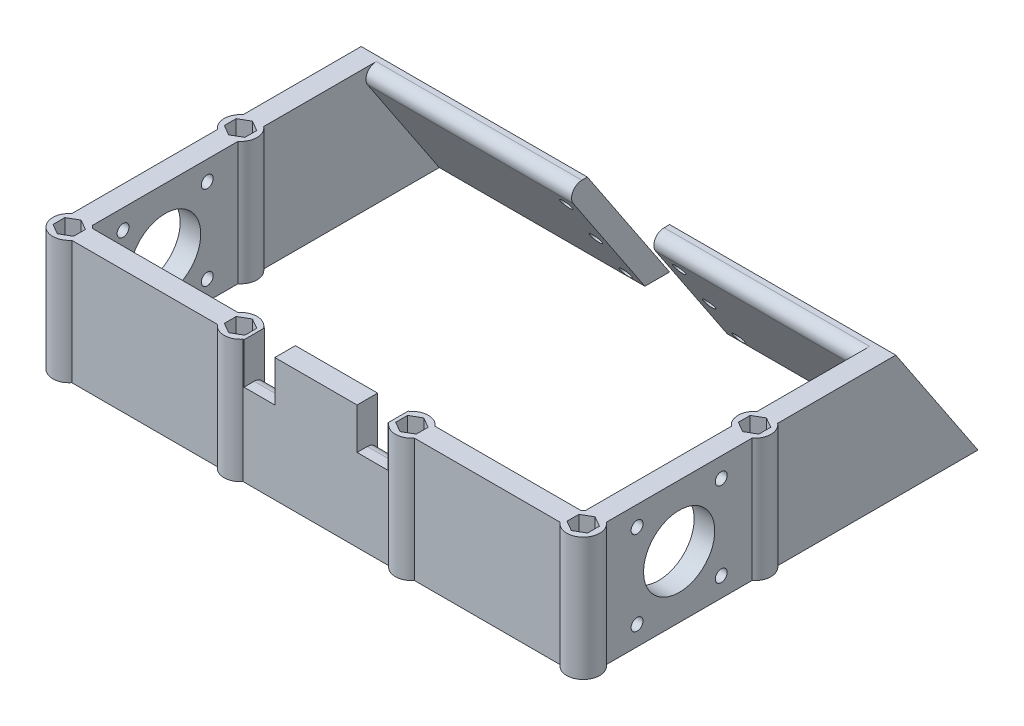
SolidWorks part; units mm, degrees
material "TPU"
ref_plane "Front Plane" through (0, 0, 0) normal (0, 0, 1) x (1, 0, 0)
ref_plane "Top Plane" through (0, 0, 0) normal (0, 1, 0) x (1, 0, 0)
ref_plane "Right Plane" through (0, 0, 0) normal (1, 0, 0) x (0, 0, -1)
sketch "Sketch4" plane through (0, 0, 0) normal (0, 1, 0) x (1, 0, 0)
  line L0 (0, 0) -> (0, -54.2428)
  line L1 (0, -114.3) -> (52.1261, -114.3) construction
  line L2 (165.1, -107.1594) -> (165.1, -62.1739)
  line L3 (165.1, 0) -> (158.75, 0)
  line L4 (158.75, 0) -> (158.75, -54.2428)
  line L7 (6.35, 0) -> (0, 0)
  line L8 (3.175, -111.125) -> (56.0917, -111.125) construction
  line L9 (56.0917, -111.125) -> (109.0083, -111.125) construction
  line L10 (109.0083, -111.125) -> (161.925, -111.125) construction
  line L11 (161.925, -111.125) -> (161.925, -58.2083) construction
  line L12 (6.35, -107.1594) -> (6.35, -62.1739)
  line L13 (6.35, -54.2428) -> (6.35, 0)
  line L14 (0, -62.1739) -> (0, -114.3) construction
  line L15 (0, -62.1739) -> (0, -107.1594)
  line L16 (7.1406, -114.3) -> (52.1261, -114.3)
  line L17 (52.1261, -107.95) -> (7.1406, -107.95)
  line L18 (60.0572, -114.3) -> (105.0428, -114.3) construction
  line L19 (60.0572, -114.3) -> (105.0428, -114.3)
  line L20 (105.0428, -107.95) -> (60.0572, -107.95)
  line L21 (112.9739, -114.3) -> (165.1, -114.3) construction
  line L22 (112.9739, -114.3) -> (157.9594, -114.3)
  line L23 (158.75, -62.1739) -> (158.75, -107.1594)
  line L24 (165.1, -54.2428) -> (165.1, 0)
  line L26 (157.9594, -107.95) -> (112.9739, -107.95)
  line L27 (0, -56.3752) -> (0, -60.0414)
  line L28 (0, -60.0414) -> (3.175, -61.8745)
  line L29 (3.175, -61.8745) -> (6.35, -60.0414)
  line L30 (6.35, -60.0414) -> (6.35, -56.3752)
  line L31 (6.35, -56.3752) -> (3.175, -54.5422)
  line L32 (3.175, -54.5422) -> (0, -56.3752)
  line L33 (3.175, -107.4588) -> (0, -109.2919)
  line L34 (0, -109.2919) -> (0, -112.9581)
  line L35 (0, -112.9581) -> (3.175, -114.7912)
  line L36 (3.175, -114.7912) -> (6.35, -112.9581)
  line L37 (6.35, -112.9581) -> (6.35, -109.2919)
  line L38 (6.35, -109.2919) -> (3.175, -107.4588)
  line L39 (56.0917, -107.4588) -> (52.9167, -109.2919)
  line L40 (52.9167, -109.2919) -> (52.9167, -112.9581)
  line L41 (52.9167, -112.9581) -> (56.0917, -114.7912)
  line L42 (56.0917, -114.7912) -> (59.2667, -112.9581)
  line L43 (59.2667, -112.9581) -> (59.2667, -109.2919)
  line L44 (59.2667, -109.2919) -> (56.0917, -107.4588)
  line L45 (109.0083, -107.4588) -> (105.8333, -109.2919)
  line L46 (105.8333, -109.2919) -> (105.8333, -112.9581)
  line L47 (105.8333, -112.9581) -> (109.0083, -114.7912)
  line L48 (109.0083, -114.7912) -> (112.1833, -112.9581)
  line L49 (112.1833, -112.9581) -> (112.1833, -109.2919)
  line L50 (112.1833, -109.2919) -> (109.0083, -107.4588)
  line L51 (161.925, -107.4588) -> (158.75, -109.2919)
  line L52 (158.75, -109.2919) -> (158.75, -112.9581)
  line L53 (158.75, -112.9581) -> (161.925, -114.7912)
  line L54 (161.925, -114.7912) -> (165.1, -112.9581)
  line L55 (165.1, -112.9581) -> (165.1, -109.2919)
  line L56 (165.1, -109.2919) -> (161.925, -107.4588)
  line L57 (161.925, -54.5422) -> (158.75, -56.3752)
  line L58 (158.75, -56.3752) -> (158.75, -60.0414)
  line L59 (158.75, -60.0414) -> (161.925, -61.8745)
  line L60 (161.925, -61.8745) -> (165.1, -60.0414)
  line L61 (165.1, -60.0414) -> (165.1, -56.3752)
  line L62 (165.1, -56.3752) -> (161.925, -54.5422)
  arc A6 (0, -54.2428) -> (0, -62.1739) centre (3.175, -58.2083) ccw
  arc A7 (6.35, -62.1739) -> (6.35, -54.2428) centre (3.175, -58.2083) ccw
  arc A8 (0, -107.1594) -> (7.1406, -114.3) centre (3.175, -111.125) ccw
  arc A9 (60.0572, -107.95) -> (52.1261, -107.95) centre (56.0917, -111.125) ccw
  arc A10 (52.1261, -114.3) -> (60.0572, -114.3) centre (56.0917, -111.125) ccw
  arc A11 (105.0428, -114.3) -> (112.9739, -114.3) centre (109.0083, -111.125) ccw
  arc A12 (112.9739, -107.95) -> (105.0428, -107.95) centre (109.0083, -111.125) ccw
  arc A13 (157.9594, -114.3) -> (165.1, -107.1594) centre (161.925, -111.125) ccw
  arc A14 (158.75, -54.2428) -> (158.75, -62.1739) centre (161.925, -58.2083) ccw
  arc A15 (165.1, -62.1739) -> (165.1, -54.2428) centre (161.925, -58.2083) ccw
  arc A16 (6.35, -107.1594) -> (7.1406, -107.95) centre (3.175, -111.125) cw
  arc A17 (158.75, -107.1594) -> (157.9594, -107.95) centre (161.925, -111.125) ccw
  circle A18 centre (3.175, -58.2083) radius 3.175 construction
  circle A19 centre (3.175, -111.125) radius 3.175 construction
  circle A20 centre (56.0917, -111.125) radius 3.175 construction
  circle A21 centre (109.0083, -111.125) radius 3.175 construction
  circle A22 centre (161.925, -111.125) radius 3.175 construction
  circle A23 centre (161.925, -58.2083) radius 3.175 construction
  point P30 (161.925, 0)
  point P51 (3.175, 0)
  dimension "D6" = 6.35
  dimension "D8" = 5.08
  dimension "D10" = 10.16
  dimension "D11" = 5.08
  dimension "D12" = 5.08
  dimension "D13" = 10.16
  dimension "D14" = 10.16
  dimension "D15" = 6.35
  dimension "D16" = 6.35
  dimension "D17" = 6.35
  dimension "D18" = 6.35
  dimension "D19" = 6.35
  dimension "D2" = 6.35
  dimension "D3" = 6.35
  dimension "D4" = 165.1
  dimension "D5" = 114.3
  dimension "D7" = 3.175
  dimension "D9" = 6.35
extrude "Boss-Extrude2" add sketch "Sketch4" along normal blind 38.1
chamfer "Chamfer2" distance 38.1 distance2 25.4 2 edges at (161.925, 38.1, 0) (3.175, 38.1, 0) first distance on face at (161.925, 19.05, 0) first distance on face at (3.175, 19.05, 0)
sketch "Sketch6" plane through (0, 0, 114.3) normal (0, 0, 1) x (1, 0, 0)
  line L0 (60.325, 38.1) -> (60.325, 25.4)
  line L1 (60.0572, 38.1) -> (105.0428, 38.1) construction
  line L2 (60.325, 25.4) -> (69.85, 25.4)
  line L3 (69.85, 25.4) -> (69.85, 38.1)
  line L4 (95.25, 38.1) -> (95.25, 25.4)
  line L5 (95.25, 25.4) -> (104.775, 25.4)
  line L6 (104.775, 25.4) -> (104.775, 38.1)
  line L7 (95.25, 38.1) -> (104.775, 38.1)
  line L8 (60.325, 38.1) -> (69.85, 38.1)
  line L9 (60.0572, 38.1) -> (60.325, 38.1) construction
  line L10 (104.775, 38.1) -> (105.0428, 38.1) construction
  dimension "D1" = 9.525
  dimension "D2" = 9.525
  dimension "D3" = 12.7
  dimension "D4" = 12.7
  dimension "D5" = 25.4
extrude "Cut-Extrude3" cut sketch "Sketch6" against normal through all
sketch "Sketch7" plane through (165.1, 0, 0) normal (1, 0, 0) x (0, 0, -1)
  line L0 (-71.6667, 32.05) -> (-97.6667, 6.05) construction
  line L1 (-71.6667, 32.05) -> (-71.6667, 6.05) construction
  line L2 (-71.6667, 6.05) -> (-97.6667, 6.05) construction
  line L3 (-97.6667, 6.05) -> (-97.6667, 32.05) construction
  line L4 (-97.6667, 32.05) -> (-71.6667, 32.05) construction
  line L6 (-116.205, 38.1) -> (-116.205, 0) construction
  line L7 (-116.205, 19.05) -> (-84.6667, 19.05) construction
  line L8 (-84.6667, 19.05) -> (-84.6667, 38.1) construction
  line L9 (-107.1594, 38.1) -> (-62.1739, 38.1) construction
  circle A0 centre (-84.6667, 19.05) radius 10.9855
  circle A1 centre (-71.6667, 32.05) radius 1.8415
  circle A2 centre (-71.6667, 6.05) radius 1.8415
  circle A3 centre (-97.6667, 6.05) radius 1.8415
  circle A4 centre (-97.6667, 32.05) radius 1.8415
  dimension "D2" = 21.971
  dimension "D3" = 3.683
  dimension "D1" = 26
extrude "Cut-Extrude4" cut sketch "Sketch7" against normal through all
sketch "Sketch8" plane through (0, 0, 0) normal (0, 0.5547, -0.8321) x (-1, 0, 0)
  line L0 (-165.1, 45.7905) -> (-95.25, 45.7905)
  line L1 (-95.25, 45.7905) -> (-95.25, 0)
  line L2 (-95.25, 0) -> (-165.1, 0)
  line L3 (-165.1, 0) -> (-165.1, 45.7905)
  line L4 (-69.85, 45.7905) -> (0, 45.7905)
  line L5 (0, 45.7905) -> (0, 0)
  line L6 (0, 0) -> (-69.85, 0)
  line L7 (-69.85, 0) -> (-69.85, 45.7905)
extrude "Boss-Extrude3" add sketch "Sketch8" along normal blind 6.35
sketch "Sketch9" plane through (165.1, 0, 0) normal (1, 0, 0) x (0, 0, -1)
  line L0 (-25.4, 38.1) -> (-17.7682, 38.1)
  line L1 (-20.1165, 41.6223) -> (5.2835, 3.5223) construction
  line L2 (-17.7682, 38.1) -> (-20.1165, 41.6223)
  line L3 (-20.1165, 41.6223) -> (-25.4, 38.1)
extrude "Cut-Extrude5" cut sketch "Sketch9" against normal through all and the other way through all
sketch "Sketch10" plane through (165.1, 0, 0) normal (1, 0, 0) x (0, 0, -1)
  line L0 (0, 0) -> (7.6318, 0)
  line L1 (7.6318, 0) -> (5.2835, 3.5223)
  line L2 (-17.7682, 38.1) -> (5.2835, 3.5223) construction
  line L3 (5.2835, 3.5223) -> (0, 0)
extrude "Boss-Extrude4" add sketch "Sketch10" against normal up to surface (69.85 mm away) up to face at (95.25, 19.9306, 9.4712)
sketch "Sketch11" plane through (0, 0, 0) normal (-1, 0, 0) x (0, 0, 1)
  line L0 (-5.2835, 3.5223) -> (-7.6318, 0)
  line L1 (-7.6318, 0) -> (0, 0)
  line L2 (0, 0) -> (-5.2835, 3.5223)
extrude "Boss-Extrude5" add sketch "Sketch11" against normal up to surface (69.85 mm away) up to face at (69.85, 19.9306, 9.4712)
sketch "Sketch12" plane through (0, 3.5223, -5.2835) normal (0, 0.5547, -0.8321) x (-1, 0, 0)
  line L0 (0, 41.5572) -> (-69.85, 41.5572) construction
  line L1 (-69.85, -4.2333) -> (0, -4.2333) construction
  line L2 (-69.85, 41.5572) -> (-69.85, -4.2333) construction
  line L3 (-95.25, -4.2333) -> (-95.25, 41.5572) construction
  circle A0 centre (-65.0875, 35.2072) radius 1.8288
  circle A1 centre (-65.0875, 2.1167) radius 1.8288
  circle A2 centre (-100.0125, 35.2072) radius 1.8288
  circle A3 centre (-100.0125, 2.1167) radius 1.8288
  dimension "D1" = 3.6576
  dimension "D2" = 3.6576
  dimension "D3" = 6.35
  dimension "D4" = 6.35
  dimension "D5" = 4.7625
  dimension "D6" = 4.7625
extrude "Cut-Extrude6" cut sketch "Sketch12" against normal through all
sketch "Sketch13" plane through (0, 3.5223, -5.2835) normal (0, 0.5547, -0.8321) x (-1, 0, 0)
  line L0 (-100.0125, 35.2072) -> (-100.0125, 2.1167) construction
  line L1 (-165.1, 41.5572) -> (-165.1, -4.2333) construction
  line L2 (-82.55, 95.1033) -> (-82.55, -4.2333) construction
  line L5 (-69.85, 95.1033) -> (-95.25, 95.1033) construction
  line L9 (-95.25, -4.2333) -> (-95.25, 41.5572) construction
  circle A0 centre (-161.925, 35.2072) radius 1.8288
  circle A1 centre (-161.925, 18.6619) radius 1.8288
  circle A2 centre (-100.0125, 18.6619) radius 1.8288
  circle A4 centre (-100.0125, 2.1167) radius 1.8288 construction
  circle A5 centre (-3.175, 18.6619) radius 1.8288
  circle A6 centre (-3.175, 35.2072) radius 1.8288
  circle A7 centre (-65.0875, 18.6619) radius 1.8288
  point P15 (0, 0)
  point P16 (0, 0)
  point P20 (-82.55, -2.818)
  dimension "D1" = 3.6576
  dimension "D2" = 3.175
  dimension "D3" = 4.7625
  dimension "D4" = 16.5453
extrude "Cut-Extrude7" cut sketch "Sketch13" against normal blind 12.7
fillet "Fillet1" radius 3.175 4 edges at (38.1, 38.1, 25.4) (127, 38.1, 25.4) (65.0875, 25.4, 107.95) (100.0125, 25.4, 107.95)
